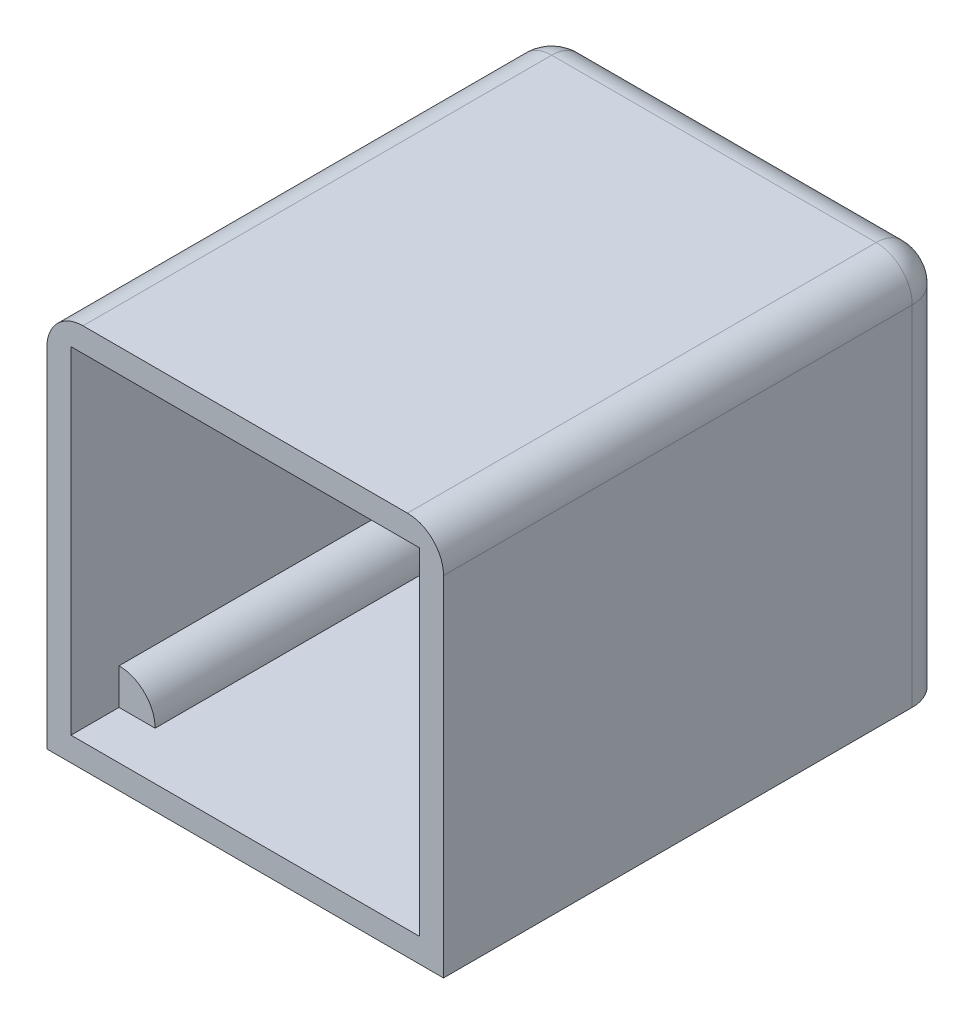
SolidWorks part; units mm, degrees
ref_plane "前视基准面" through (0, 0, 0) normal (0, 0, 1) x (1, 0, 0)
ref_plane "上视基准面" through (0, 0, 0) normal (0, 1, 0) x (1, 0, 0)
ref_plane "右视基准面" through (0, 0, 0) normal (1, 0, 0) x (0, 0, -1)
sketch "草图1" plane through (0, 0, 0) normal (0, 0, 1) x (1, 0, 0)
  line L0 (-16.0572, 12.6569) -> (-16.0572, -19.3431)
  line L1 (-14.0572, 10.6569) -> (14.9428, 10.6569)
  line L2 (-14.0572, 10.6569) -> (-14.0572, -17.3431)
  line L3 (-14.0572, -17.3431) -> (14.9428, -17.3431)
  line L4 (14.9428, 10.6569) -> (14.9428, -17.3431)
  line L5 (-16.0572, -19.3431) -> (16.9428, -19.3431)
  line L6 (16.9428, 12.6569) -> (16.9428, -19.3431)
  line L7 (-16.0572, 12.6569) -> (16.9428, 12.6569)
  dimension "D1" = 29
  dimension "D2" = 28
  dimension "D3" = 2
extrude "凸台-拉伸1" add sketch "草图1" along normal blind 40
ref_plane "基准面1" through (0, 0, 0) normal (0, 0, -1) x (-1, 0, 0)
sketch "草图2" plane through (0, 0, 0) normal (0, 0, -1) x (-1, 0, 0)
  line L0 (-16.9428, -13.1618) -> (16.0572, -13.1618) construction
  line L1 (-16.9428, 12.6569) -> (16.0572, 12.6569)
  line L2 (-16.9428, 12.6569) -> (-16.9428, -19.3431)
  line L3 (-16.9428, -19.3431) -> (16.0572, -19.3431)
  line L4 (16.0572, 12.6569) -> (16.0572, -19.3431)
  line L8 (-5.4428, -13.1618) -> (-5.4428, -10.1618)
  line L9 (-5.4428, -10.1618) -> (4.5572, -10.1618)
  line L10 (4.5572, -10.1618) -> (4.5572, -13.1618)
  line L11 (-5.4428, -13.1618) -> (4.5572, -13.1618)
  dimension "D2" = 11.5
  dimension "D3" = 3
extrude "凸台-拉伸2" add sketch "草图2" along normal blind 2
sketch "草图5" plane through (0, 0, 0) normal (0, 0, -1) x (-1, 0, 0)
  line L0 (-14.9428, 10.6569) -> (14.0572, 10.6569) construction
  line L1 (14.0572, 10.6569) -> (14.0572, -17.3431) construction
  line L3 (-14.9428, -17.3431) -> (-14.9428, 10.6569) construction
  line L4 (14.0572, -17.3431) -> (-14.9428, -17.3431) construction
  line L5 (14.0572, -17.3431) -> (-14.9428, -17.3431) construction
  line L6 (11.0572, 10.6569) -> (14.0572, 10.6569)
  line L7 (14.0572, 10.6569) -> (14.0572, 7.6569)
  line L8 (-11.9428, 10.6569) -> (-14.9428, 10.6569)
  line L9 (-14.9428, 10.6569) -> (-14.9428, 7.6569)
  line L10 (-14.9428, -14.3431) -> (-14.9428, -17.3431)
  line L11 (-14.9428, -17.3431) -> (-11.9428, -17.3431)
  line L13 (11.0572, -17.3431) -> (14.0572, -17.3431)
  line L14 (14.0572, -17.3431) -> (14.0572, -14.3431)
  arc A0 (11.0572, 10.6569) -> (14.0572, 7.6569) centre (14.0572, 10.6569) ccw
  arc A1 (-11.9428, 10.6569) -> (-14.9428, 7.6569) centre (-14.9428, 10.6569) cw
  arc A2 (14.0572, -14.3431) -> (11.0572, -17.3431) centre (14.0572, -17.3431) ccw
  arc A3 (-14.9428, -14.3431) -> (-11.9428, -17.3431) centre (-14.9428, -17.3431) cw
  dimension "D1" = 3
  dimension "D2" = 3
  dimension "D3" = 3
  dimension "D4" = 3
extrude "凸台-拉伸3" add sketch "草图5" against normal offset from surface (36 mm away) 4 up to face at (0.4428, -3.3431, 40)
fillet "圆角1" radius 3 3 edges at (16.9428, 12.6569, 19) (0.4428, 12.6569, -2) (-16.0572, 12.6569, 19) type face fillet first side face at (0.4428, 12.6569, 19) second side face at (0.4428, -3.3431, -2) second side face at (16.9428, -3.3431, 19) second side face at (-16.0572, -3.3431, 19)
fillet "圆角2" radius 3 1 edges at (16.9428, -4.8431, -2) type face fillet first side face at (16.9428, -4.8431, 19) second side face at (0.4428, -4.8431, -2)
fillet "圆角3" radius 3 1 edges at (-16.0572, -4.8431, -2) type face fillet first side face at (-1.0572, -4.8431, -2) second side face at (-16.0572, -4.8431, 19)
